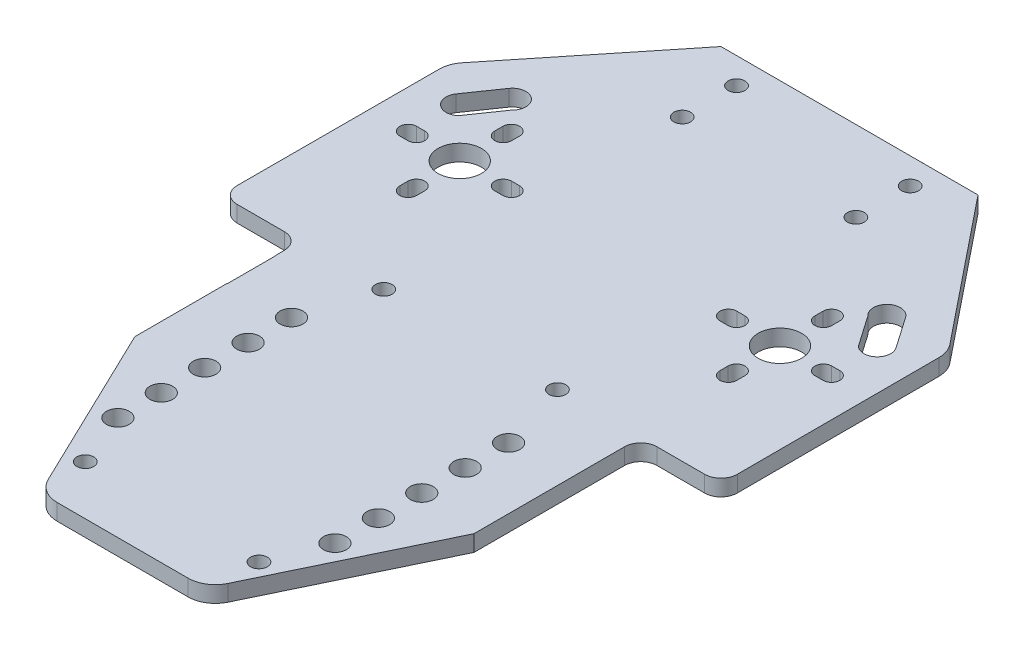
SolidWorks part; units mm, degrees
material "Thornel Mat VMA"
ref_plane "Front Plane" through (0, 0, 0) normal (0, 0, 1) x (1, 0, 0)
ref_plane "Top Plane" through (0, 0, 0) normal (0, 1, 0) x (1, 0, 0)
ref_plane "Right Plane" through (0, 0, 0) normal (1, 0, 0) x (0, 0, -1)
sketch "Sketch1" plane through (0, 0, 0) normal (0, 1, 0) x (1, 0, 0)
  line L0 (0, 0) -> (0, -27.5) construction
  line L1 (0, 0) -> (121.6069, 0) construction
  line L2 (37.5, 0) -> (39, 0) construction
  line L3 (37.5, 1.55) -> (39, 1.55)
  line L4 (37.5, -1.55) -> (39, -1.55)
  line L5 (29.5, -8) -> (29.5, -9.5) construction
  line L6 (31.05, -8) -> (31.05, -9.5)
  line L7 (27.95, -8) -> (27.95, -9.5)
  line L8 (21.5, 0) -> (20, 0) construction
  line L9 (21.5, -1.55) -> (20, -1.55)
  line L10 (21.5, 1.55) -> (20, 1.55)
  line L11 (29.5, 8) -> (29.5, 9.5) construction
  line L12 (27.95, 8) -> (27.95, 9.5)
  line L13 (31.05, 8) -> (31.05, 9.5)
  line L14 (20, -72.5) -> (20, -64.5) construction
  line L19 (-29.5, 8) -> (-29.5, 9.5) construction
  line L20 (-27.95, 8) -> (-27.95, 9.5)
  line L21 (-31.05, 8) -> (-31.05, 9.5)
  line L22 (-21.5, 0) -> (-20, 0) construction
  line L23 (-21.5, -1.55) -> (-20, -1.55)
  line L24 (-21.5, 1.55) -> (-20, 1.55)
  line L25 (-29.5, -8) -> (-29.5, -9.5) construction
  line L26 (-31.05, -8) -> (-31.05, -9.5)
  line L27 (-27.95, -8) -> (-27.95, -9.5)
  line L28 (-37.5, 0) -> (-39, 0) construction
  line L29 (-37.5, 1.55) -> (-39, 1.55)
  line L30 (-37.5, -1.55) -> (-39, -1.55)
  line L31 (-31.3246, -40.5321) -> (-31.3246, -32.4375)
  line L34 (-38.4806, -33.6183) -> (-38.4806, -40.5321)
  line L35 (31.3246, -40.5321) -> (31.3246, -32.4375)
  line L36 (38.4806, -33.6183) -> (38.4806, -40.5321)
  line L37 (-36.8266, 7.1221) -> (-32.8384, 12.8748)
  line L38 (29.5, 0) -> (50.8627, -25.4591) construction
  line L41 (46, 48.4159) -> (-46, 48.4159)
  line L44 (46, 48.4159) -> (46.1488, -91.633)
  line L47 (46.1488, -91.633) -> (-46.1487, -91.584)
  line L50 (-46, 48.4159) -> (-46.1487, -91.584)
  line L53 (-36.5402, 16.1211) -> (-40.5285, 10.3684)
  line L59 (-959, -57) -> (49041, -57) construction
  line L63 (36.8266, 7.1221) -> (32.8384, 12.8748)
  line L64 (36.5402, 16.1211) -> (40.5285, 10.3684)
  circle A0 centre (29.5, 0) radius 4
  arc A1 (37.5, 1.55) -> (37.5, -1.55) centre (37.5, 0) ccw
  arc A2 (39, -1.55) -> (39, 1.55) centre (39, 0) ccw
  arc A3 (31.05, -8) -> (27.95, -8) centre (29.5, -8) ccw
  arc A4 (27.95, -9.5) -> (31.05, -9.5) centre (29.5, -9.5) ccw
  arc A5 (21.5, -1.55) -> (21.5, 1.55) centre (21.5, 0) ccw
  arc A6 (20, 1.55) -> (20, -1.55) centre (20, 0) ccw
  arc A7 (27.95, 8) -> (31.05, 8) centre (29.5, 8) ccw
  arc A8 (31.05, 9.5) -> (27.95, 9.5) centre (29.5, 9.5) ccw
  circle A13 centre (-29.5, 0) radius 4
  arc A14 (-27.95, 8) -> (-31.05, 8) centre (-29.5, 8) cw
  arc A15 (-31.05, 9.5) -> (-27.95, 9.5) centre (-29.5, 9.5) cw
  arc A16 (-21.5, -1.55) -> (-21.5, 1.55) centre (-21.5, 0) cw
  arc A17 (-20, 1.55) -> (-20, -1.55) centre (-20, 0) cw
  arc A18 (-31.05, -8) -> (-27.95, -8) centre (-29.5, -8) cw
  arc A19 (-27.95, -9.5) -> (-31.05, -9.5) centre (-29.5, -9.5) cw
  arc A20 (-37.5, 1.55) -> (-37.5, -1.55) centre (-37.5, 0) cw
  arc A21 (-39, -1.55) -> (-39, 1.55) centre (-39, 0) cw
  circle A22 centre (16, 27.5) radius 1.55
  circle A23 centre (16, -27.5) radius 1.55
  circle A24 centre (-16, -27.5) radius 1.55
  circle A25 centre (-16, 27.5) radius 1.55
  circle A76 centre (-16, 37.5) radius 1.55
  circle A77 centre (16, 37.5) radius 1.55
  circle A78 centre (20, -72.5) radius 2.1
  circle A79 centre (-20, -72.5) radius 2.1
  circle A83 centre (-20, -40.5) radius 2.1
  circle A84 centre (20, -40.5) radius 2.1
  circle A85 centre (20, -64.5) radius 2.1
  circle A86 centre (-20, -64.5) radius 2.1
  circle A87 centre (20, -56.5) radius 2.1
  circle A88 centre (-20, -56.5) radius 2.1
  circle A89 centre (20, -48.5) radius 2.1
  circle A90 centre (-20, -48.5) radius 2.1
  circle A91 centre (-16, -82.5) radius 1.55
  circle A92 centre (16, -82.5) radius 1.55
  arc A93 (-38.4806, -40.5321) -> (-31.3246, -40.5321) centre (-34.9026, -40.5321) ccw
  arc A94 (-31.3246, -32.4375) -> (-38.4806, -33.6183) centre (-35, -32.4375) ccw
  arc A95 (38.4806, -40.5321) -> (31.3246, -40.5321) centre (34.9026, -40.5321) cw
  arc A96 (31.3246, -32.4375) -> (38.4806, -33.6183) centre (35, -32.4375) cw
  arc A103 (-40.5285, 10.3684) -> (-36.8266, 7.1221) centre (-38.4922, 8.9566) ccw
  arc A106 (-36.5402, 16.1211) -> (-32.8384, 12.8748) centre (-34.5039, 14.7093) cw
  arc A107 (36.5402, 16.1211) -> (32.8384, 12.8748) centre (34.5039, 14.7093) ccw
  arc A108 (40.5285, 10.3684) -> (36.8266, 7.1221) centre (38.4922, 8.9566) cw
  point P8 (38.25, 0)
  point P18 (29.5, -8.75)
  point P25 (20.75, 0)
  point P32 (29.5, 8.75)
  point P37 (29.5, 0)
  point P51 (0, 32.5)
  point P55 (-29.5, 8.75)
  point P62 (-20.75, 0)
  point P69 (-29.5, -8.75)
  point P76 (-38.25, 0)
  dimension "D1" = 8
  dimension "D2" = 1.55
  dimension "D4" = 8
  dimension "D5" = 4
  dimension "D6" = 92
  dimension "D7" = 140
  dimension "D8" = 2
  dimension "D9" = 59
  dimension "D10" = 3.1
  dimension "D11" = 40
  dimension "D12" = 27.5
  dimension "D13" = 8
  dimension "D15" = 7
  dimension "D27" = 4.2
  dimension "D28" = 100
  dimension "D3" = 1.5
  dimension "D14" = 35
  dimension "D16" = 7
  dimension "D23" = 50
extrude "Boss-Extrude1" [suppressed] add sketch "Sketch1" along normal blind 3
sketch "草图7" [suppressed] plane through (0, 0, 0) normal (0, 1, 0) x (1, 0, 0)
  line L0 (0, 0) -> (0, -97.058) construction
  line L1 (-27.95, -9.5) -> (-27.95, -8) construction
  line L2 (22.2054, 32.5) -> (-23.2593, 32.5) construction
  line L3 (-31.05, -8) -> (-31.05, -9.5) construction
  line L4 (-37.5, 1.55) -> (-39, 1.55)
  line L5 (-39, -1.55) -> (-37.5, -1.55)
  line L6 (-37.5, 1.55) -> (-39, 1.55)
  line L7 (-39, -1.55) -> (-37.5, -1.55)
  line L8 (-27.95, 8) -> (-27.95, 9.5)
  line L9 (-31.05, 9.5) -> (-31.05, 8)
  line L10 (-27.95, 8) -> (-27.95, 9.5)
  line L11 (-31.05, 9.5) -> (-31.05, 8)
  line L12 (-21.5, -1.55) -> (-20, -1.55)
  line L13 (-20, 1.55) -> (-21.5, 1.55)
  line L14 (-21.5, -1.55) -> (-20, -1.55)
  line L15 (-20, 1.55) -> (-21.5, 1.55)
  line L16 (-27.95, -9.5) -> (-27.95, -8)
  line L17 (-31.05, -8) -> (-31.05, -9.5)
  line L20 (37.5, -1.55) -> (39, -1.55)
  line L21 (39, 1.55) -> (37.5, 1.55)
  line L22 (37.5, -1.55) -> (39, -1.55)
  line L23 (39, 1.55) -> (37.5, 1.55)
  line L24 (27.95, -8) -> (27.95, -9.5)
  line L25 (31.05, -9.5) -> (31.05, -8)
  line L26 (27.95, -8) -> (27.95, -9.5)
  line L27 (31.05, -9.5) -> (31.05, -8)
  line L28 (21.5, 1.55) -> (20, 1.55)
  line L29 (20, -1.55) -> (21.5, -1.55)
  line L30 (21.5, 1.55) -> (20, 1.55)
  line L31 (20, -1.55) -> (21.5, -1.55)
  line L32 (31.05, 8) -> (31.05, 9.5)
  line L33 (27.95, 9.5) -> (27.95, 8)
  line L34 (31.05, 8) -> (31.05, 9.5)
  line L35 (27.95, 9.5) -> (27.95, 8)
  circle A0 centre (29.5, 0) radius 4 construction
  circle A1 centre (29.5, 0) radius 4
  circle A3 centre (-20, -72.5) radius 1.55
  circle A4 centre (-29.5, 0) radius 4
  circle A5 centre (-29.5, 0) radius 4
  circle A6 centre (16, 27.5) radius 1.55
  circle A7 centre (16, 27.5) radius 1.55
  circle A8 centre (-16, 27.5) radius 1.55
  circle A9 centre (-16, 27.5) radius 1.55
  circle A12 centre (16, 37.5) radius 1.55
  circle A13 centre (-16, 37.5) radius 1.55
  circle A14 centre (-16, -27.5) radius 1.55
  circle A15 centre (20, -72.5) radius 1.55
  arc A16 (-31.05, -9.5) -> (-27.95, -9.5) centre (-29.5, -9.5) ccw construction
  arc A18 (-37.5, -1.55) -> (-37.5, 1.55) centre (-37.5, 0) ccw
  arc A19 (-39, 1.55) -> (-39, -1.55) centre (-39, 0) ccw
  arc A20 (-37.5, -1.55) -> (-37.5, 1.55) centre (-37.5, 0) ccw
  arc A21 (-39, 1.55) -> (-39, -1.55) centre (-39, 0) ccw
  arc A23 (-27.95, -8) -> (-31.05, -8) centre (-29.5, -8) ccw construction
  arc A24 (-31.05, 8) -> (-27.95, 8) centre (-29.5, 8) ccw
  arc A25 (-27.95, 9.5) -> (-31.05, 9.5) centre (-29.5, 9.5) ccw
  arc A26 (-31.05, 8) -> (-27.95, 8) centre (-29.5, 8) ccw
  arc A27 (-27.95, 9.5) -> (-31.05, 9.5) centre (-29.5, 9.5) ccw
  arc A28 (-21.5, 1.55) -> (-21.5, -1.55) centre (-21.5, 0) ccw
  arc A29 (-20, -1.55) -> (-20, 1.55) centre (-20, 0) ccw
  arc A30 (-21.5, 1.55) -> (-21.5, -1.55) centre (-21.5, 0) ccw
  arc A31 (-20, -1.55) -> (-20, 1.55) centre (-20, 0) ccw
  arc A32 (-31.05, -9.5) -> (-27.95, -9.5) centre (-29.5, -9.5) ccw
  arc A33 (-27.95, -8) -> (-31.05, -8) centre (-29.5, -8) ccw
  circle A34 centre (16, -27.5) radius 1.55
  arc A36 (37.5, 1.55) -> (37.5, -1.55) centre (37.5, 0) ccw
  arc A37 (39, -1.55) -> (39, 1.55) centre (39, 0) ccw
  arc A38 (37.5, 1.55) -> (37.5, -1.55) centre (37.5, 0) ccw
  arc A39 (39, -1.55) -> (39, 1.55) centre (39, 0) ccw
  arc A40 (31.05, -8) -> (27.95, -8) centre (29.5, -8) ccw
  arc A41 (27.95, -9.5) -> (31.05, -9.5) centre (29.5, -9.5) ccw
  arc A42 (31.05, -8) -> (27.95, -8) centre (29.5, -8) ccw
  arc A43 (27.95, -9.5) -> (31.05, -9.5) centre (29.5, -9.5) ccw
  arc A44 (21.5, -1.55) -> (21.5, 1.55) centre (21.5, 0) ccw
  arc A45 (20, 1.55) -> (20, -1.55) centre (20, 0) ccw
  arc A46 (21.5, -1.55) -> (21.5, 1.55) centre (21.5, 0) ccw
  arc A47 (20, 1.55) -> (20, -1.55) centre (20, 0) ccw
  arc A48 (27.95, 8) -> (31.05, 8) centre (29.5, 8) ccw
  arc A49 (31.05, 9.5) -> (27.95, 9.5) centre (29.5, 9.5) ccw
  arc A50 (27.95, 8) -> (31.05, 8) centre (29.5, 8) ccw
  arc A51 (31.05, 9.5) -> (27.95, 9.5) centre (29.5, 9.5) ccw
  dimension "D4" = 3.1
  dimension "D6" = 20
  dimension "D7" = 5
  dimension "D9" = 3.1
  dimension "D16" = 32
  dimension "D17" = 55
  dimension "D5" = 100
  dimension "D8" = 0
  dimension "D1" = 0
  dimension "D2" = 0
  dimension "D3" = 0
  dimension "D10" = 0
  dimension "D11" = 0
  dimension "D12" = 0
  dimension "D13" = 0
  dimension "D14" = 0
  dimension "D15" = 0
extrude "凸台-拉伸1" add sketch "Sketch1<2>" along normal blind 3 contours L41 L50 L47 L44 A79 A78 A23 A22 A0 A2 L4 A1 L3 A4 L7 A3 L6 A6 L10 A5 L9 A8 L13 A7 L12 A13 L21 A15 L20 A14 L24 A17 L23 A16 region at (0.0029, 0, 21.6938)
sketch "Sketch1<2>" plane through (0, 0, 0) normal (0, 1, 0) x (1, 0, 0) same geometry as "Sketch1"
sketch "草图8" plane through (0, 0, 0) normal (0, 1, 0) x (1, 0, 0)
  line L0 (-11.1069, -100.1389) -> (-60.5812, 2.6993)
  line L1 (-60.5812, 2.6993) -> (-60.5812, -100.1389)
  line L2 (-60.5812, -100.1389) -> (-11.1069, -100.1389)
  line L3 (0, -21.5721) -> (0, 8.1084) construction
  line L4 (60.5812, -100.1389) -> (11.1069, -100.1389)
  line L5 (60.5812, 2.6993) -> (60.5812, -100.1389)
  line L6 (11.1069, -100.1389) -> (60.5812, 2.6993)
  line L7 (-55.5478, 2.6866) -> (-14.4304, 53.8253)
  line L8 (-14.4304, 53.8253) -> (-55.5478, 53.8253)
  line L9 (-55.5478, 53.8253) -> (-55.5478, 2.6866)
  line L10 (55.5478, 53.8253) -> (55.5478, 2.6866)
  line L11 (14.4304, 53.8253) -> (55.5478, 53.8253)
  line L12 (55.5478, 2.6866) -> (14.4304, 53.8253)
  line L13 (-46.0806, -27.4419) -> (-31.3889, -27.4419)
  line L14 (-46, 48.4159) -> (-46.1487, -91.584) construction
  line L15 (-31.3889, -27.4419) -> (-31.3889, -57.9803)
  line L16 (46.0806, -27.4419) -> (31.2972, -27.4419)
  line L17 (31.2972, -27.4419) -> (31.2972, -58.171)
  line L18 (-31.3246, -40.5321) -> (-31.3246, -32.4375) construction
  line L19 (-31.3246, -40.5321) -> (-31.3246, -32.4375)
extrude "切除-拉伸1" cut sketch "草图8" along normal through all contours L1 L2 L0 | L8 L9 L7 | L12 L10 L11 | L6 L4 L5 | L16 L17 L6 | L15 L13 L0 region at (-44.0897, 0, 65.8595) region at (-36.2861, 0, 37.6214) region at (44.0897, 0, 65.8595) region at (36.225, 0, 37.6849) region at (-41.842, 0, -36.779) region at (41.842, 0, -36.779)
fillet "圆角1" radius 5 6 edges at (-15.2146, 1.5, 91.6005) (15.2069, 1.5, 91.6166) (46.036, 1.5, -14.5166) (18.7797, 1.5, -48.4159) (-18.7797, 1.5, -48.4159) (-46.036, 1.5, -14.5166)
fillet "圆角2" radius 3 4 edges at (-46.0806, 1.5, 27.4419) (-31.3889, 1.5, 27.4419) (31.2972, 1.5, 27.4419) (46.0806, 1.5, 27.4419)
sketch "草图9" plane through (0, 0, 0) normal (0, -1, 0) x (1, 0, 0)
  line L0 (-6.7665, -48.4159) -> (-21.3535, -48.4159)
  line L1 (16.3842, -48.4159) -> (-16.3842, -48.4159) construction
  line L2 (-21.3535, -48.4159) -> (-23.6809, -42.3202)
  line L3 (-20.2808, -46.549) -> (-44.9345, -15.8866) construction
  line L4 (-23.6809, -42.3202) -> (23.6809, -42.3202)
  line L5 (20.2808, -46.549) -> (44.9345, -15.8866) construction
  line L6 (23.6809, -42.3202) -> (18.7797, -48.4159)
  line L7 (18.7797, -48.4159) -> (-6.7665, -48.4159)
extrude "切除-拉伸2" cut sketch "草图9" against normal blind 10
